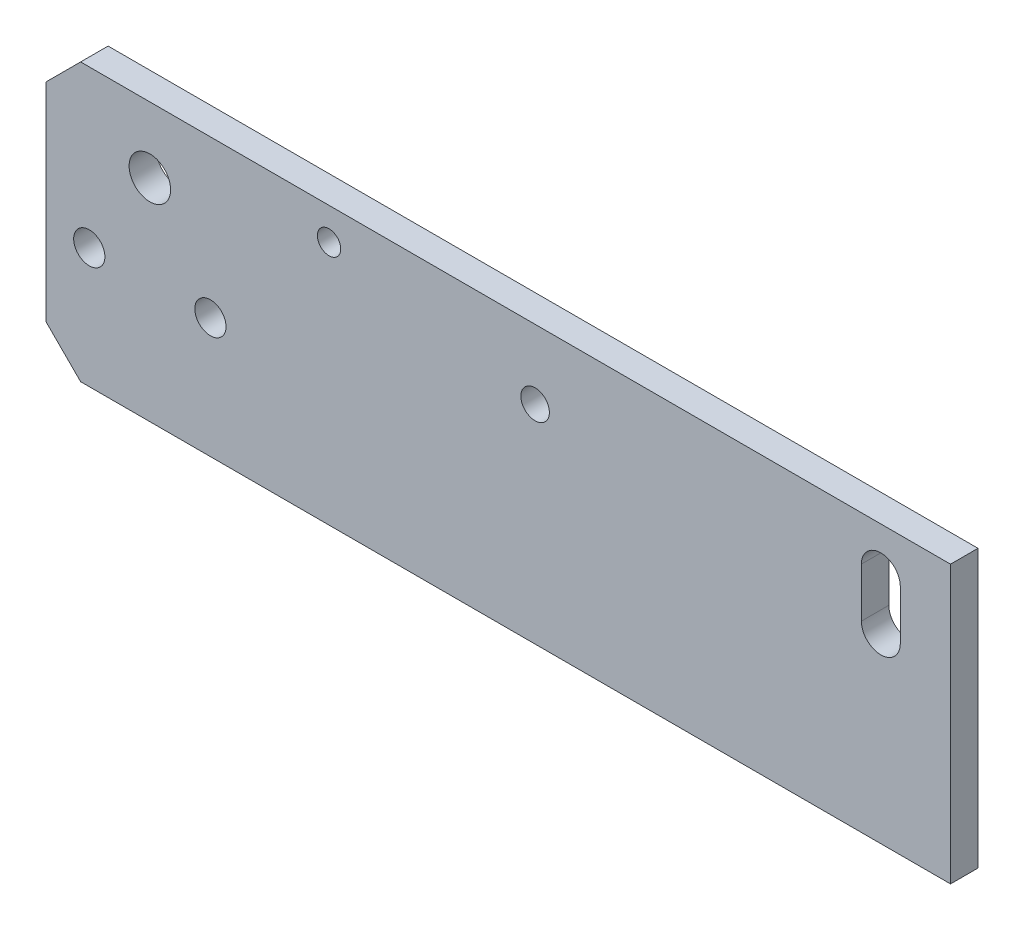
SolidWorks part; units mm, degrees
ref_plane "Front" through (0, 0, 0) normal (0, 0, 1) x (1, 0, 0)
ref_plane "Top" through (0, 0, 0) normal (0, 1, 0) x (1, 0, 0)
ref_plane "Right" through (0, 0, 0) normal (1, 0, 0) x (0, 0, -1)
ref_axis "side-side" through (80.9, 0, 0) along (-1, 0, 0)
ref_axis "up-down" through (0, 50, 0) along (0, -1, 0)
ref_axis "front-back" through (0, 0, -80.9) along (0, 0, 1)
sketch "Sketch1" plane through (0, 0, 0) normal (0, 0, 1) x (1, 0, 0)
  line L0 (28, 410.2) -> (28, 0) construction
  line L1 (28, 33) -> (-76.516, 33)
  line L2 (28, 33) -> (28, 1)
  line L3 (28, 1) -> (-76.516, 1)
  line L4 (-76.516, 33) -> (-76.516, 1)
  line L5 (19.9481, 27.8529) -> (19.9481, 22.1471) construction
  line L6 (22.1981, 27.8529) -> (22.1981, 22.1471)
  line L7 (-20, 25) -> (20, 25) construction
  line L8 (17.6981, 27.8529) -> (17.6981, 22.1471)
  circle A0 centre (-20, 25) radius 2.25 construction
  circle A1 centre (-64.516, 25.4) radius 2.6 construction
  circle A2 centre (-64.516, 25.4) radius 2.4 construction
  circle A3 centre (-64.516, 25.4) radius 2.4
  circle A4 centre (-20, 25) radius 2.25 construction
  circle A5 centre (20, 25) radius 2.25 construction
  circle A6 centre (20, 25) radius 2.25 construction
  arc A7 (-64.3741, 28.574) -> (-64.4312, 22.224) centre (-20, 25) ccw construction
  arc A8 (19.8981, 22.1471) -> (19.8981, 27.8529) centre (-20, 25) ccw construction
  arc A9 (22.1981, 27.8529) -> (17.6981, 27.8529) centre (19.9481, 27.8529) ccw
  arc A10 (17.6981, 22.1471) -> (22.1981, 22.1471) centre (19.9481, 22.1471) ccw
  circle A11 centre (-57.516, 14.9) radius 1.8034
  circle A12 centre (-71.516, 14.9) radius 1.8034
  point P23 (19.9481, 25)
  point P28 (-64.516, 25.4)
  dimension "D1" = 8
  dimension "D3" = 12
  dimension "D4" = 6.35
  dimension "D6" = 8.18
  dimension "D10" = 3.6068
  dimension "D2" = 32
  dimension "D5" = 8.18
  dimension "D7" = 0.1019
  dimension "D8" = 0.05
  dimension "D9" = 4.5
extrude "Boss-Extrude1" add sketch "Sketch1" against normal blind 3.175
hole_wizard "M4x0.7 Tapped Hole1" positions "Sketch2" profile "Sketch3" tap size "M4x0.7" standard "ANSI Metric" end condition through all
sketch "Sketch2" plane through (0, 0, -3.175) normal (0, 0, -1) x (-1, 0, 0)
  point P0 (20, 25)
sketch "Sketch3" plane through (-20, 25, -3.175) normal (1, 0, 0) x (0, 1, 0)
  line L0 (0, 0) -> (0, 3.175)
  line L1 (0, 3.175) -> (1.65, 3.175)
  line L2 (1.65, 3.175) -> (1.65, 0)
  line L5 (1.65, 0) -> (0, 0)
  line L11 (0, -6.35) -> (0, 107.95) construction
  dimension "Thread Major Dia." = 3.3
  dimension "Thru Tap Drill Depth" = 3.175
chamfer "Chamfer1" distance 4 angle 45 2 edges at (-76.516, 1, -1.5875) (-76.516, 33, -1.5875)
hole_wizard "#6-32 Tapped Hole1" positions "Sketch4" profile "Sketch6" tap size "#6-32" standard "ANSI Inch" end condition through all
sketch "Sketch4" plane through (0, 0, 0) normal (0, 0, 1) x (1, 0, 0)
  line L0 (-40, 0) -> (-40, 410.2) construction
  line L1 (28, 33) -> (-72.516, 33) construction
  point P0 (-43.81, 29.3078)
  dimension "D1" = 3.81
  dimension "D2" = 3.6922
sketch "Sketch6" plane through (-43.81, 29.3078, 0) normal (1, 0, 0) x (0, -1, 0)
  line L0 (0, 0) -> (0, 3.175)
  line L1 (0, 3.175) -> (1.3525, 3.175)
  line L2 (1.3525, 3.175) -> (1.3525, 0)
  line L5 (1.3525, 0) -> (0, 0)
  line L11 (0, -6.35) -> (0, 107.95) construction
  dimension "Thread Major Dia." = 2.7051
  dimension "Thru Tap Drill Depth" = 3.175
